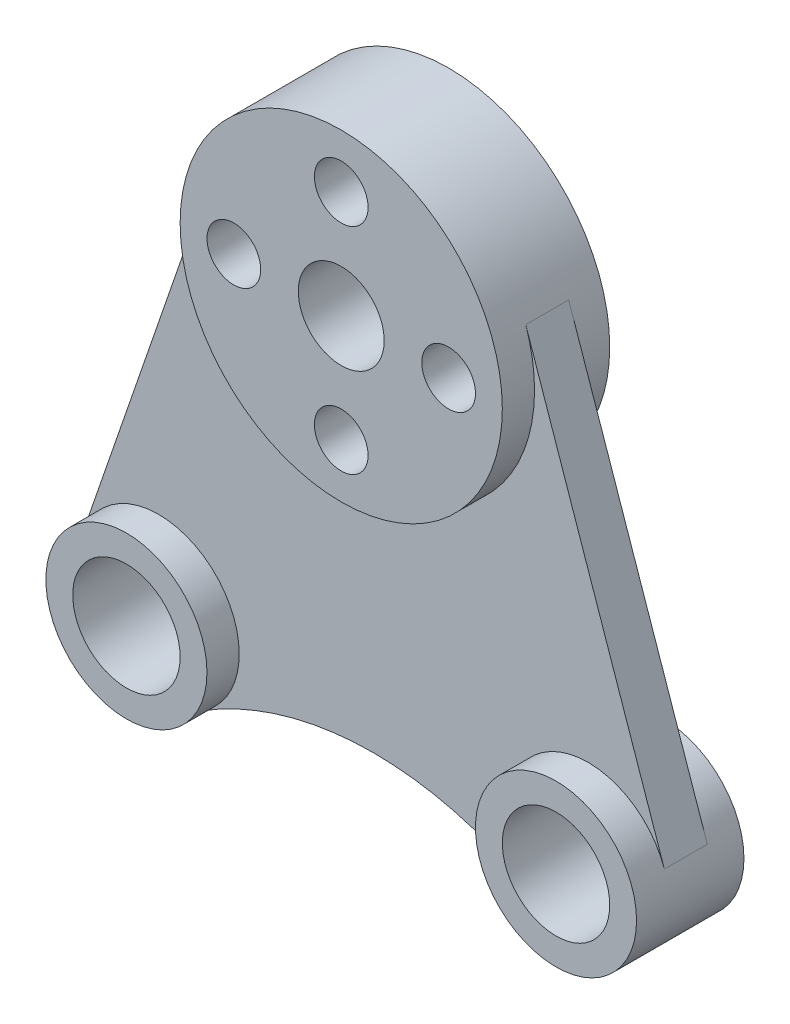
SolidWorks part; units mm, degrees
note: The reader was unsure of these and kept them because the rebuilt part matched: shared geometry of "Sketch1<3>".
ref_plane "Front Plane" through (0, 0, 0) normal (0, 0, 1) x (1, 0, 0)
ref_plane "Top Plane" through (0, 0, 0) normal (0, 1, 0) x (1, 0, 0)
ref_plane "Right Plane" through (0, 0, 0) normal (1, 0, 0) x (0, 0, -1)
sketch "Sketch1" plane through (0, 0, 0) normal (0, 0, 1) x (1, 0, 0)
  line L0 (0, 0) -> (21252.9325, 0) construction
  line L1 (0, 0) -> (0, 21252.9325) construction
  line L2 (28.3617, 9.7781) -> (54.1809, -65.1109)
  line L3 (-28.3617, 9.7781) -> (-54.1809, -65.1109)
  circle A0 centre (0, 0) radius 8
  circle A1 centre (0, 0) radius 20 construction
  circle A2 centre (0, 0) radius 30
  circle A3 centre (40, -70) radius 10
  circle A4 centre (40, -70) radius 15
  circle A5 centre (-40, -70) radius 10
  circle A6 centre (-40, -70) radius 15
  circle A7 centre (20, 0) radius 5
  circle A8 centre (0, -20) radius 5
  circle A9 centre (-20, 0) radius 5
  circle A10 centre (0, 20) radius 5
  arc A11 (-32, -82.6886) -> (32, -82.6886) centre (0, -133.4429) cw
  point P25 (0, 0)
  dimension "D1" = 20
  dimension "D2" = 30
  dimension "D5" = 60
  dimension "D6" = 40
  dimension "D7" = 16
  dimension "D8" = 10
  dimension "D10" = 60
  dimension "D3" = 80
  dimension "D4" = 70
  dimension "D9" = 4
extrude "Boss-Extrude1" add sketch "Sketch1" along normal mid plane 20 contours A2 A10 A9 A8 A7 A0 | A6 A5 | A4 A3 | A3
extrude "Boss-Extrude2" add sketch "Sketch1<3>" along normal mid plane 8 contours A6 A11 A4 L2 A2 L3
sketch "Sketch1<3>" plane through (0, 0, 0) normal (0, 0, 1) x (1, 0, 0) same geometry as "Sketch1"
